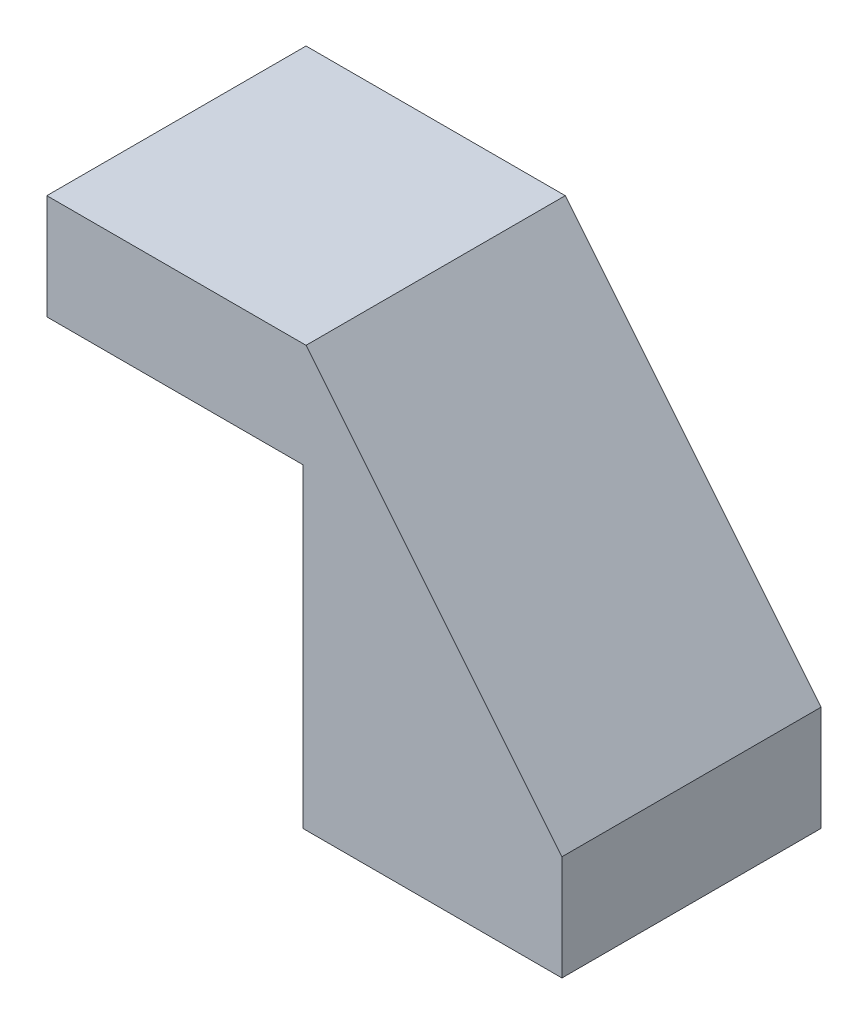
SolidWorks part; units mm, degrees
ref_plane "Front Plane" through (0, 0, 0) normal (0, 0, 1) x (1, 0, 0)
ref_plane "Top Plane" through (0, 0, 0) normal (0, 1, 0) x (1, 0, 0)
ref_plane "Right Plane" through (0, 0, 0) normal (1, 0, 0) x (0, 0, -1)
sketch "Sketch1" plane through (0, 0, 0) normal (0, 1, 0) x (1, 0, 0)
  line L1 (0, 0) -> (7.9, 0)
  line L2 (0, 0) -> (0, 7.9)
  line L3 (0, 7.9) -> (7.9, 7.9)
  line L4 (7.9, 0) -> (7.9, 7.9)
  dimension "D1" = 7.9
  dimension "D2" = 7.9
extrude "Boss-Extrude1" add sketch "Sketch1" along normal blind 3.2
sketch "Sketch2" plane through (0, 0, 0) normal (-1, 0, 0) x (0, 0, 1)
  line L1 (-7.9, 0) -> (0, 0)
  line L2 (-7.9, 0) -> (-7.9, 9.6)
  line L3 (-7.9, 9.6) -> (0, 9.6)
  line L4 (0, 0) -> (0, 9.6)
  dimension "D1" = 9.6
extrude "Boss-Extrude2" add sketch "Sketch2" against normal blind 0.1
sketch "Sketch3" plane through (0, 9.6, 0) normal (0, 1, 0) x (1, 0, 0)
  line L1 (0.1, 0) -> (-7.8, 0)
  line L2 (0.1, 0) -> (0.1, 7.9)
  line L3 (0.1, 7.9) -> (-7.8, 7.9)
  line L4 (-7.8, 0) -> (-7.8, 7.9)
  dimension "D1" = 7.9
  dimension "D2" = 7.9
extrude "Boss-Extrude3" add sketch "Sketch3" along normal blind 3.2
sketch "Sketch4" plane through (0, 0, 0) normal (0, 0, 1) x (1, 0, 0)
  line L0 (0.1, 12.8) -> (7.9, 3.2)
  line L1 (7.9, 3.2) -> (0.1, 3.2)
  line L2 (0.1, 3.2) -> (0.1, 12.8)
extrude "Boss-Extrude4" add sketch "Sketch4" against normal up to surface (7.9 mm away) up to face at (0.05, 6.4, -7.9)
